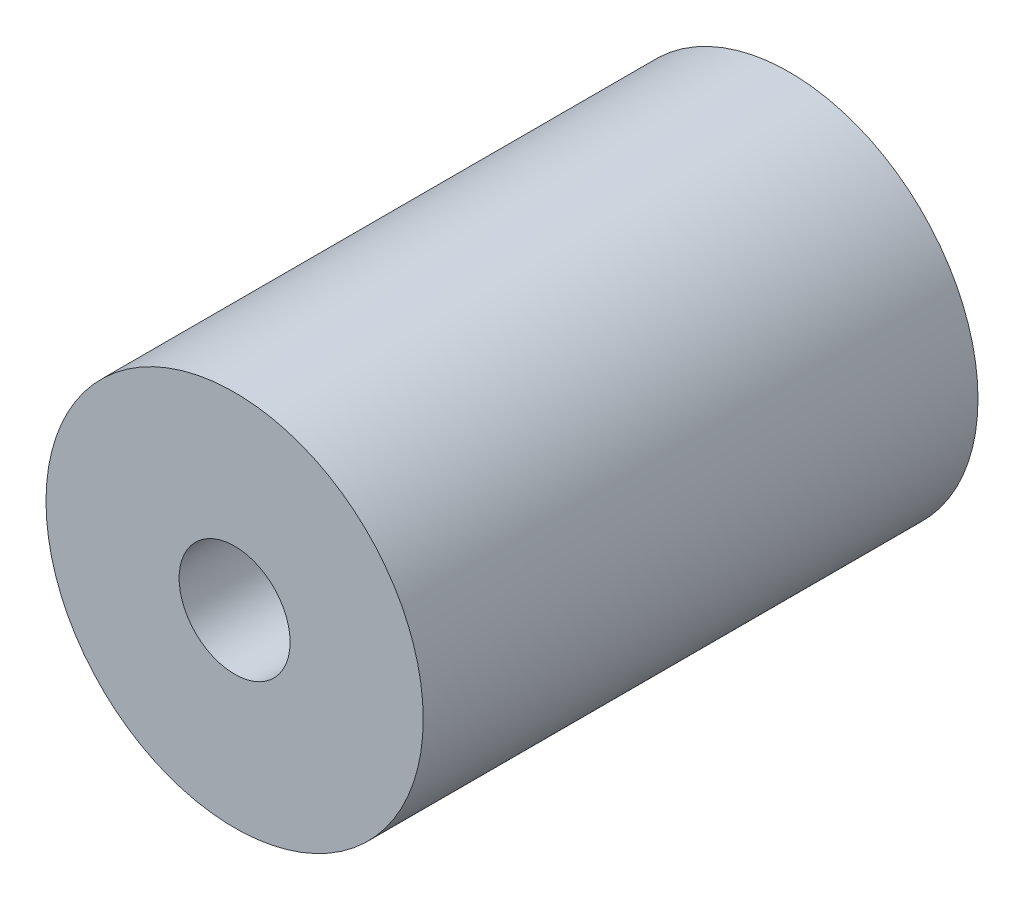
SolidWorks part; units mm, degrees
ref_plane "Front Plane" through (0, 0, 0) normal (0, 0, 1) x (1, 0, 0)
ref_plane "Top Plane" through (0, 0, 0) normal (0, 1, 0) x (1, 0, 0)
ref_plane "Right Plane" through (0, 0, 0) normal (1, 0, 0) x (0, 0, -1)
sketch "Sketch1" plane through (0, 0, 0) normal (0, 0, 1) x (1, 0, 0)
  circle A0 centre (0, 0) radius 2.5
  circle A1 centre (0, 0) radius 8.5
  dimension "D1" = 5
  dimension "D2" = 6
extrude "Boss-Extrude1" add sketch "Sketch1" along normal mid plane 25
